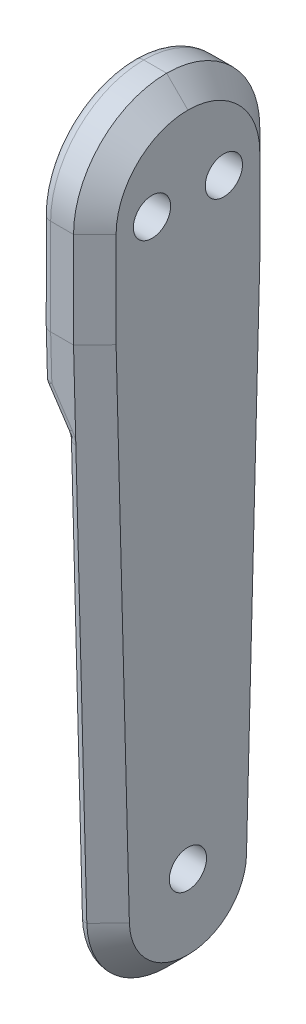
SolidWorks part; units mm, degrees
material "ABS"
ref_plane "Front Plane" through (0, 0, 0) normal (0, 0, 1) x (1, 0, 0)
ref_plane "Top Plane" through (0, 0, 0) normal (0, 1, 0) x (1, 0, 0)
ref_plane "Right Plane" through (0, 0, 0) normal (1, 0, 0) x (0, 0, -1)
sketch "Sketch1" plane through (0, 0, 0) normal (1, 0, 0) x (0, 0, -1)
  line L1 (-10, 10) -> (10, 10)
  line L2 (-10, 10) -> (-10, -10)
  line L3 (-10, -10) -> (10, -10)
  line L4 (10, 10) -> (10, -10)
  line L5 (-10, 10) -> (10, -10) construction
  line L6 (-10, -10) -> (10, 10) construction
  point P0 (0, 0)
  dimension "D1" = 20
  dimension "D2" = 20
extrude "Boss-Extrude1" add sketch "Sketch1" along normal blind 20
sketch "Sketch2" plane through (20, 0, 0) normal (1, 0, 0) x (0, 0, -1)
  line L1 (-22.5, 35) -> (22.5, 35)
  line L2 (-22.5, 35) -> (-22.5, -35)
  line L3 (-22.5, -35) -> (22.5, -35)
  line L4 (22.5, 35) -> (22.5, -35)
  line L5 (-22.5, 35) -> (22.5, -35) construction
  line L6 (-22.5, -35) -> (22.5, 35) construction
  point P0 (0, 0)
  dimension "D1" = 45
  dimension "D2" = 70
extrude "Boss-Extrude2" add sketch "Sketch2" along normal blind 10.3
sketch "Sketch4" plane through (30.3, 0, 0) normal (1, 0, 0) x (0, 0, -1)
  line L0 (0, 7.65) -> (0, 8.1702) construction
  line L1 (7.65, 7.65) -> (-7.65, 7.65) construction
  line L17 (3.6, -26.55) -> (-3.6, -26.55) construction
  line L18 (-7.65, 7.65) -> (7.65, 7.65) construction
  line L22 (-7.65, 7.65) -> (-7.65, -27.55) construction
  line L23 (-7.65, -27.55) -> (7.65, -27.55) construction
  line L24 (7.65, 7.65) -> (7.65, -27.55) construction
  line L25 (-7.65, 7.65) -> (7.65, -27.55) construction
  line L26 (-7.65, -27.55) -> (7.65, 7.65) construction
  line L27 (3.6, -26.55) -> (3.6, -28.55) construction
  line L28 (3.6, -28.55) -> (-3.6, -28.55) construction
  line L29 (-3.6, -26.55) -> (-3.6, -28.55) construction
  line L30 (3.6, -26.55) -> (-3.6, -28.55) construction
  line L31 (3.6, -28.55) -> (-3.6, -26.55) construction
  line L34 (3.6, -28.55) -> (-3.6, -28.55)
  line L35 (-3.6, -28.55) -> (-3.6, -7.3118)
  line L36 (3.6, -28.55) -> (3.6, -7.3118)
  arc A1 (3.6, -6.75) -> (-3.6, -6.75) centre (0, 0) ccw construction
  arc A2 (3.6, -7.3118) -> (-3.6, -7.3118) centre (0, 0) ccw
  point P1 (0, -27.55)
  point P7 (0, -13.75)
  point P10 (0, 7.65)
  point P14 (0, -9.95)
  dimension "D1" = 15.3
  dimension "D5" = 2
  dimension "D2" = 15.3
  dimension "D3" = 35.2
  dimension "D4" = 7.2
extrude "Cut-Extrude1" cut sketch "Sketch4" against normal blind 5.8
fillet "Fillet1" radius 3.6 2 edges at (27.4, -28.55, 3.6) (27.4, -28.55, -3.6)
fillet "Fillet2" radius 10 2 edges at (27.4, -7.3118, 3.6) (27.4, -7.3118, -3.6)
sketch "Sketch5" plane through (0, 0, 0) normal (-1, 0, 0) x (0, 0, 1)
  circle A0 centre (0, 0) radius 1.75
  dimension "D1" = 3.5
extrude "Cut-Extrude2" cut sketch "Sketch5" against normal through all
sketch "Sketch6" plane through (24.5, 0, 0) normal (1, 0, 0) x (0, 0, -1)
  line L0 (0, -19.35) -> (0, 0) construction
  line L1 (0, -25.65) -> (0, -23.15) construction
  line L2 (0, -23.15) -> (0, -21.85) construction
  line L3 (0, -21.85) -> (0, -19.35) construction
  line L5 (0, 0) -> (1.164, 0) construction
  line L6 (0, 0) -> (0, -9.35) construction
  line L7 (0, -9.35) -> (1.164, -9.35) construction
  line L8 (1.164, 0) -> (1.164, -9.35) construction
  line L9 (0, 0) -> (1.164, -9.35) construction
  line L10 (0, -9.35) -> (1.164, 0) construction
  circle A0 centre (0, -20.6) radius 1.75
  circle A1 centre (0, -9.35) radius 1.75 construction
  point P11 (0.582, -4.675)
  dimension "D5" = 3.5
  dimension "D6" = 9.35
  dimension "D7" = 3.5
  dimension "D1" = 19.35
  dimension "D2" = 2.5
  dimension "D3" = 1.3
  dimension "D4" = 2.5
extrude "Cut-Extrude3" cut sketch "Sketch6" against normal up to next
sketch "Sketch13" plane through (0, 0, 0) normal (-1, 0, 0) x (0, 0, 1)
  line L1 (-10, 10) -> (10, 10)
  line L2 (-10, 10) -> (-10, -10)
  line L3 (-10, -10) -> (10, -10)
  line L4 (10, 10) -> (10, -10)
extrude "Cut-Extrude9" cut sketch "Sketch13" against normal up to surface (20 mm away) up to face at (20, -20.6, -1.75)
sketch "Sketch14" plane through (20, 0, 0) normal (-1, 0, 0) x (0, 0, 1)
  circle A5 centre (0, 0) radius 11
  dimension "D2" = 22
extrude "Boss-Extrude3" add sketch "Sketch14" along normal blind 7 contours A5
sketch "Sketch15" plane through (0, 35, 0) normal (0, 1, 0) x (1, 0, 0)
  line L1 (20, 22.5) -> (30.3, 22.5)
  line L2 (20, 22.5) -> (20, -22.5)
  line L3 (20, -22.5) -> (30.3, -22.5)
  line L4 (30.3, 22.5) -> (30.3, -22.5)
extrude "Cut-Extrude10" cut sketch "Sketch15" against normal blind 12.5
sketch "Sketch18" plane through (0, -35, 0) normal (0, -1, 0) x (1, 0, 0)
  line L1 (20, 22.5) -> (30.3, 22.5)
  line L2 (20, 22.5) -> (20, -22.5)
  line L3 (20, -22.5) -> (30.3, -22.5)
  line L4 (30.3, 22.5) -> (30.3, -22.5)
  line L5 (30.3, 22.5) -> (20, 22.5) construction
  line L6 (30.3, 22.5) -> (30.3, -22.5) construction
extrude "Boss-Extrude4" add sketch "Sketch18" along normal blind 95.5
sketch "Sketch20" plane through (20, 0, 0) normal (-1, 0, 0) x (0, 0, 1)
  line L0 (0, 0) -> (0, -100) construction
  line L1 (22.5, 22.5) -> (22.5, -130.5) construction
  line L2 (-22.5, -130.5) -> (22.5, -130.5)
  line L3 (-22.5, -130.5) -> (-22.5, -33.5)
  line L4 (-22.5, -33.5) -> (22.5, -33.5)
  line L5 (22.5, -130.5) -> (22.5, -33.5)
  dimension "D1" = 100
  dimension "D2" = 97
extrude "Cut-Extrude12" cut sketch "Sketch20" against normal blind 4.3
sketch "Sketch21" plane through (24.3, 0, 0) normal (-1, 0, 0) x (0, 0, 1)
  line L0 (0, -130.5) -> (0, -109.5) construction
  line L1 (-22.5, -130.5) -> (22.5, -130.5) construction
  circle A0 centre (0, -109.5) radius 5.025
  dimension "D2" = 10.05
  dimension "D1" = 21
extrude "Boss-Extrude5" add sketch "Sketch21" along normal blind 8.8
sketch "Sketch24" plane through (13, 0, 0) normal (-1, 0, 0) x (0, 0, 1)
  circle A2 centre (0, 0) radius 8
  circle A3 centre (0, 0) radius 8
  dimension "D1" = 3
extrude "Cut-Extrude14" cut sketch "Sketch24" against normal blind 7.6
sketch "Sketch25" plane through (0, 0, -22.5) normal (0, 0, -1) x (-1, 0, 0)
  line L6 (-24.3, -130.5) -> (-24.3, -33.5)
  line L7 (-24.3, -33.5) -> (-20, -33.5)
  line L8 (-20, -33.5) -> (-20, 22.5)
  line L9 (-20, 22.5) -> (-30.3, 22.5)
  line L10 (-30.3, 22.5) -> (-30.3, -130.5)
  line L11 (-30.3, -130.5) -> (-24.3, -130.5)
  line L12 (-24.3, -130.5) -> (-24.3, -33.5)
  line L13 (-24.3, -33.5) -> (-20, -33.5)
  line L14 (-20, -33.5) -> (-20, 22.5)
  line L15 (-20, 22.5) -> (-30.3, 22.5)
  line L16 (-30.3, 22.5) -> (-30.3, -130.5)
  line L17 (-30.3, -130.5) -> (-24.3, -130.5)
  dimension "D1" = 0
extrude "Cut-Extrude15" cut sketch "Sketch25" against normal blind 5
sketch "Sketch26" plane through (0, 0, 22.5) normal (0, 0, 1) x (1, 0, 0)
  line L6 (20, 22.5) -> (20, -33.5)
  line L7 (20, -33.5) -> (24.3, -33.5)
  line L8 (24.3, -33.5) -> (24.3, -130.5)
  line L9 (24.3, -130.5) -> (30.3, -130.5)
  line L10 (30.3, -130.5) -> (30.3, 22.5)
  line L11 (30.3, 22.5) -> (20, 22.5)
  line L12 (20, 22.5) -> (20, -33.5)
  line L13 (20, -33.5) -> (24.3, -33.5)
  line L14 (24.3, -33.5) -> (24.3, -130.5)
  line L15 (24.3, -130.5) -> (30.3, -130.5)
  line L16 (30.3, -130.5) -> (30.3, 22.5)
  line L17 (30.3, 22.5) -> (20, 22.5)
  dimension "D1" = 0
extrude "Cut-Extrude16" cut sketch "Sketch26" against normal blind 5
sketch "Sketch28" plane through (20, 0, 0) normal (-1, 0, 0) x (0, 0, 1)
  line L0 (0, 11) -> (0, 18) construction
  line L1 (17.5, 22.5) -> (17.5, -33.5) construction
  line L2 (-17.5, 22.5) -> (17.5, 22.5)
  line L3 (-17.5, 22.5) -> (-17.5, 18)
  line L4 (-17.5, 18) -> (17.5, 18)
  line L5 (17.5, 22.5) -> (17.5, 18)
  circle A0 centre (0, 0) radius 11 construction
  dimension "D1" = 7
extrude "Cut-Extrude17" cut sketch "Sketch28" against normal through all
sketch "Sketch31" plane through (13, 0, 0) normal (-1, 0, 0) x (0, 0, 1)
  line L0 (0, 0) -> (-2.5, 0) construction
  line L1 (-2.5, 0) -> (-11, 0) construction
  line L2 (0, 0) -> (2.5, 0) construction
  line L3 (2.5, 0) -> (11, 0) construction
  circle A1 centre (0, 0) radius 11 construction
  circle A2 centre (-6.75, 0) radius 3.35
  circle A3 centre (6.75, 0) radius 3.35
  dimension "D2" = 6.7
  dimension "D4" = 6.7
  dimension "D1" = 2.5
  dimension "D3" = 2.5
extrude "Boss-Extrude6" add sketch "Sketch31" against normal up to surface (7.6 mm away) up to face at (20.6, 0, 8)
sketch "Sketch36" plane through (30.3, 0, 0) normal (1, 0, 0) x (0, 0, -1)
  line L1 (-10.2624, 8.7262) -> (10.2624, 8.7262)
  line L2 (-10.2624, 8.7262) -> (-10.2624, -29.3718)
  line L3 (-10.2624, -29.3718) -> (10.2624, -29.3718)
  line L4 (10.2624, 8.7262) -> (10.2624, -29.3718)
  point P5 (0, 8.7262)
  arc M7 (-6.1069, -5.3971) -> (6.1069, -5.3971) centre (0, 0) cw
  arc M8 (6.1069, -5.3971) -> (3.6, -12.0193) centre (13.6, -12.0193) ccw
  line M9 (3.6, -12.0193) -> (3.6, -24.95)
  arc M10 (3.6, -24.95) -> (0, -28.55) centre (0, -24.95) cw
  arc M11 (0, -28.55) -> (-3.6, -24.95) centre (0, -24.95) cw
  line M12 (-3.6, -24.95) -> (-3.6, -12.0193)
  arc M13 (-3.6, -12.0193) -> (-6.1069, -5.3971) centre (-13.6, -12.0193) ccw
  arc M14 (-6.1069, -5.3971) -> (6.1069, -5.3971) centre (0, 0) cw
  arc M16 (-6.1069, -5.3971) -> (6.1069, -5.3971) centre (0, 0) cw
extrude "Boss-Extrude7" add sketch "Sketch36" against normal blind 6 contours M16 M14 M13 M12 M11 M10 M9 M8 M7 | L4 L1 L2 L3 M16 M7 M8 M9 M10 M11 M12 M13 M14 | L2 L1 L4 L3 region at (30.3, 8.2935, 0) region at (30.3, -7.2742, 0)
sketch "Sketch33" plane through (13, 0, 0) normal (-1, 0, 0) x (0, 0, 1)
  line L0 (-3.4, 0) -> (-10.1, 0) construction
  line L1 (3.4, 0) -> (10.1, 0) construction
  arc A0 (-7.2844, -3.3071) -> (-7.2844, 3.3071) centre (-6.75, 0) ccw construction
  arc A1 (7.2844, 3.3071) -> (7.2844, -3.3071) centre (6.75, 0) ccw construction
  circle A2 centre (-6.75, 0) radius 1.75
  circle A3 centre (6.75, 0) radius 1.75
  dimension "D3" = 3.5
  dimension "D4" = 3.5
  dimension "D1" = 6.7
  dimension "D2" = 6.7
extrude "Cut-Extrude19" cut sketch "Sketch33" against normal through all contours A2 | A3
fillet "Fillet8" radius 17.5 2 edges at (25.15, 18, 17.5) (25.15, 18, -17.5)
sketch "Sketch23" plane through (15.5, 0, 0) normal (-1, 0, 0) x (0, 0, 1)
  circle A3 centre (0, -109.5) radius 1.75
  dimension "D1" = 3.5
extrude "Cut-Extrude13" cut sketch "Sketch23" against normal through all contours A3
sketch "Sketch35" plane through (0, -130.5, 0) normal (0, -1, 0) x (1, 0, 0)
  line L4 (30.3, -17.5) -> (30.3, 17.5)
  line L5 (30.3, 17.5) -> (24.3, 17.5)
  line L6 (24.3, 17.5) -> (24.3, -17.5)
  line L7 (24.3, -17.5) -> (30.3, -17.5)
  line L8 (30.3, -17.5) -> (30.3, 17.5)
  line L9 (30.3, 17.5) -> (24.3, 17.5)
  line L10 (24.3, 17.5) -> (24.3, -17.5)
  line L11 (24.3, -17.5) -> (30.3, -17.5)
  dimension "D1" = 0
extrude "Cut-Extrude21" cut sketch "Sketch35" against normal blind 3
chamfer "Chamfer6" distance 110 angle 1.5 2 edges at (27.3, -127.5, -17.5) (27.3, -127.5, 17.5) first distance on face at (24.8667, -53.5, -17.5) first distance on face at (24.8667, -53.5, 17.5)
fillet "Fillet11" radius 15 2 edges at (27.3, -127.5, 14.6195) (27.3, -127.5, -14.6195)
chamfer "Chamfer9" distance 7 angle 32 1 edges at (20, -33.5, 0) first distance on face at (20, -20.6, -1.75)
sketch "Sketch38" plane through (13, 0, 0) normal (-1, 0, 0) x (0, 0, 1)
  circle A1 centre (0, 0) radius 11
  circle A3 centre (0, 0) radius 11
  dimension "D1" = 0
extrude "Cut-Extrude22" cut sketch "Sketch38" against normal blind 4.5
sketch "Sketch40" plane through (20, 0, 0) normal (-1, 0, 0) x (0, 0, 1)
  circle A1 centre (0, -20.6) radius 1.75
  circle A2 centre (0, -20.6) radius 1.75
  arc A4 (-7.2844, -3.3071) -> (-7.2844, 3.3071) centre (-6.75, 0) ccw
  arc A5 (-7.2844, -3.3071) -> (7.2844, -3.3071) centre (0, 0) ccw
  arc A6 (7.2844, 3.3071) -> (7.2844, -3.3071) centre (6.75, 0) ccw
  arc A7 (7.2844, 3.3071) -> (-7.2844, 3.3071) centre (0, 0) ccw
  arc A8 (-7.2844, -3.3071) -> (-7.2844, 3.3071) centre (-6.75, 0) ccw
  arc A9 (-7.2844, -3.3071) -> (7.2844, -3.3071) centre (0, 0) ccw
  arc A10 (7.2844, 3.3071) -> (7.2844, -3.3071) centre (6.75, 0) ccw
  arc A11 (7.2844, 3.3071) -> (-7.2844, 3.3071) centre (0, 0) ccw
  dimension "D1" = 0
  dimension "D2" = 0
extrude "Boss-Extrude8" add sketch "Sketch40" against normal through all
sketch "Sketch42" plane through (30.3, 0, 0) normal (1, 0, 0) x (0, 0, -1)
  circle A0 centre (-6.75, 0) radius 3.5
  circle A1 centre (6.75, 0) radius 3.5
  circle A2 centre (0, -109.5) radius 3.5
  dimension "D1" = 7
  dimension "D2" = 7
  dimension "D3" = 7
extrude "Cut-Extrude24" cut sketch "Sketch42" against normal blind 8
fillet "Fillet14" radius 2 2 edges at (24.3, -33.3814, 0) (20, -26.5, 0)
chamfer "Chamfer10" distance 4 angle 45 9 edges at (30.3, -8.5, -17.5) (30.3, 12.8744, -12.3744) (30.3, 12.8744, 12.3744) (30.3, -8.5, 17.5) (30.3, -65.1963, -16.251) (30.3, -123.2445, -10.4741) (30.3, -65.1963, 16.251) (30.3, -127.5, 0) (30.3, -123.2445, 10.4741)
fillet "Fillet13" radius 2 17 edges at (24.3, -73.4238, -16.0356) (24.3, -123.2445, -10.4741) (24.3, -123.2445, 10.4741) (20, -8.5, 17.5) (20, -8.5, -17.5) (20, 12.8744, -12.3744) (22.15, -29.9407, -17.1742) (24.3, -73.4238, 16.0356) (22.15, -29.9407, 17.1742) (20, 12.8744, 12.3744) (20, -21.7133, 17.3897) (20, -21.7133, -17.3897) (24.3, -127.5, 0) (20.0775, -26.4778, -17.2649) (24.2225, -33.4037, -17.0835) (24.2225, -33.4037, 17.0835) (20.0775, -26.4778, 17.2649)
sketch "Sketch43" plane through (24.3, 0, 0) normal (-1, 0, 0) x (0, 0, 1)
  circle A0 centre (0, -109.5) radius 5.025
  circle A1 centre (0, -109.5) radius 6
  dimension "D1" = 10.05
  dimension "D2" = 12
extrude "Boss-Extrude9" add sketch "Sketch43" along normal blind 2.4
